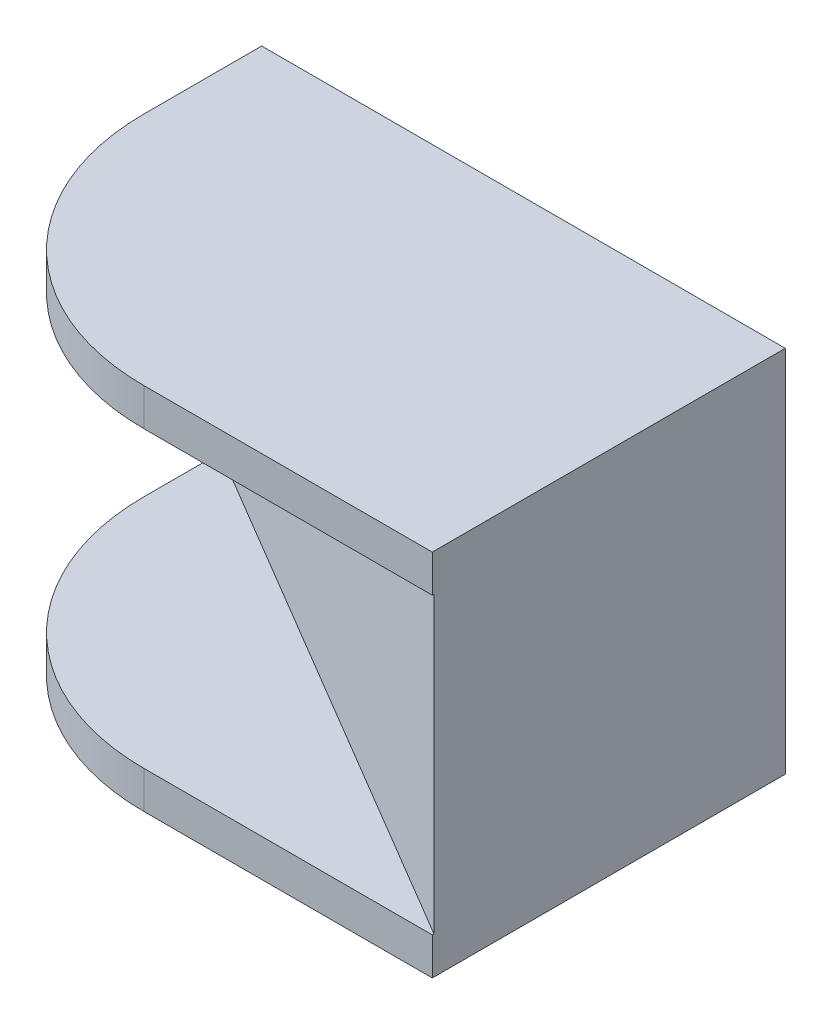
SolidWorks part; units mm, degrees
ref_plane "Front Plane" through (0, 0, 0) normal (0, 0, 1) x (1, 0, 0)
ref_plane "Top Plane" through (0, 0, 0) normal (0, 1, 0) x (1, 0, 0)
ref_plane "Right Plane" through (0, 0, 0) normal (1, 0, 0) x (0, 0, -1)
sketch "Sketch6" plane through (0, 0, 0) normal (0, 1, 0) x (1, 0, 0)
  line L1 (-22.25, 15) -> (22.25, 15)
  line L2 (-22.25, 15) -> (-22.25, -15)
  line L3 (-22.25, -15) -> (22.25, -15)
  line L4 (22.25, 15) -> (22.25, -15)
  line L5 (-22.25, 15) -> (22.25, -15) construction
  line L6 (-22.25, -15) -> (22.25, 15) construction
  point P0 (0, 0)
  dimension "D1" = 44.5
  dimension "D2" = 30
extrude "Boss-Extrude5" add sketch "Sketch6" along normal blind 31.35
ref_plane "Plane1" through (0, 15.675, 0) normal (0, 1, 0) x (1, 0, 0)
sketch "Sketch8" plane through (0, 15.675, 0) normal (0, 1, 0) x (1, 0, 0)
  line L0 (-22.25, 11.5) -> (-22.25, -15)
  line L1 (-22.25, 15) -> (-22.25, -15) construction
  line L2 (-22.25, -15) -> (22.4909, -15)
  line L3 (-22.25, -15) -> (22.25, -15) construction
  line L4 (22.4909, -15) -> (-22.25, 11.5)
  line L5 (22.25, 15) -> (-22.25, 15) construction
  point P8 (-22.25, 12.9604)
  dimension "D1" = 3.5
  dimension "D3" = 52
extrude "Cut-Extrude1" cut sketch "Sketch8" against normal offset from surface (12.5 mm away) 3.175 up to face at (0, 0, 0)
mirror "Mirror2" about plane through (0, 15.675, 0) normal (0, 1, 0) of "Cut-Extrude1"
fillet "Fillet1" radius 20 2 edges at (-22.25, 1.5875, 15) (-22.25, 29.7625, 15)
sketch "Sketch9" plane through (0, 0, -15) normal (0, 0, -1) x (-1, 0, 0)
  line L0 (22.25, 15.675) -> (-22.25, 15.675) construction
  line L1 (22.25, 31.35) -> (22.25, 0) construction
  line L2 (-22.25, 31.35) -> (-22.25, 0) construction
  circle A0 centre (2.25, 15.675) radius 2.15
  circle A1 centre (-17.75, 15.675) radius 2.15
  dimension "D1" = 4.3
  dimension "D2" = 20
  dimension "D3" = 20
extrude "Cut-Extrude2" cut sketch "Sketch9" against normal blind 8
